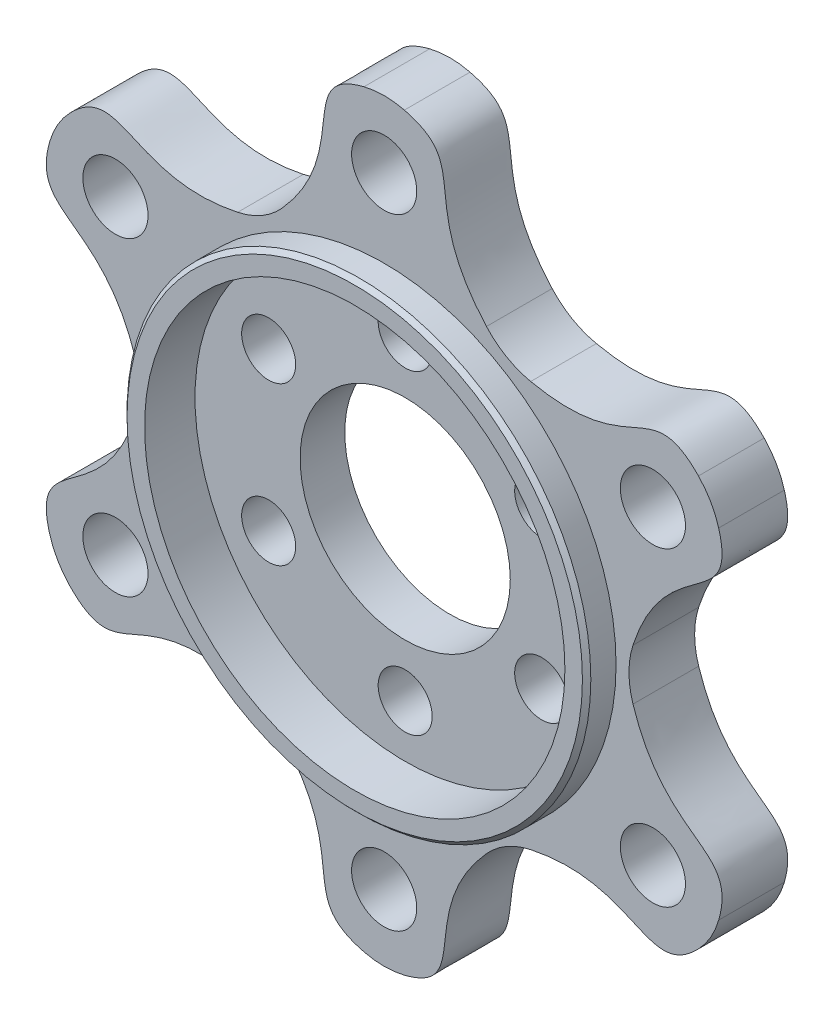
SolidWorks part; units mm, degrees
ref_plane "Front Plane" through (0, 0, 0) normal (0, 0, 1) x (1, 0, 0)
ref_plane "Top Plane" through (0, 0, 0) normal (0, 1, 0) x (1, 0, 0)
ref_plane "Right Plane" through (0, 0, 0) normal (1, 0, 0) x (0, 0, -1)
sketch "Sketch1" plane through (0, 0, 0) normal (0, 0, 1) x (1, 0, 0)
  line L0 (0, -55) -> (0, 55) construction
  line L1 (0, 0) -> (0, 45.72) construction
  circle A0 centre (0, 0) radius 12.7
  circle A1 centre (0, 0) radius 45.72
  circle A2 centre (0, 19.05) radius 3.2639
  circle A3 centre (16.4978, 9.525) radius 3.2639
  circle A4 centre (16.4978, -9.525) radius 3.2639
  circle A5 centre (0, -19.05) radius 3.2639
  circle A6 centre (-16.4978, -9.525) radius 3.2639
  circle A7 centre (-16.4978, 9.525) radius 3.2639
  circle A8 centre (0, 37.5) radius 3.937
  circle A10 centre (32.476, 18.75) radius 3.937
  circle A11 centre (32.476, -18.75) radius 3.937
  circle A12 centre (0, -37.5) radius 3.937
  circle A13 centre (-32.476, -18.75) radius 3.937
  circle A14 centre (-32.476, 18.75) radius 3.937
  point P21 (0, 0)
  point P36 (0, 0)
  dimension "D1" = 25.4
  dimension "D2" = 91.44
  dimension "D3" = 6.5278
  dimension "D6" = 7.874
  dimension "D4" = 19.05
  dimension "D8" = 37.5
  dimension "D5" = 6
  dimension "D7" = 6
extrude "Boss-Extrude3" add sketch "Sketch1" along normal blind 7.9375
sketch "Sketch2" plane through (0, 0, 7.9375) normal (0, 0, 1) x (1, 0, 0)
  line L0 (0, -55) -> (0, 55) construction
  line L1 (-32.476, 18.75) -> (0, 37.5) construction
  line L2 (-16.238, 28.125) -> (-6.35, 10.9985) construction
  line L3 (16.1981, 28.148) -> (6.3101, 11.0215) construction
  line L6 (32.476, -18.75) -> (32.476, 18.75) construction
  line L7 (32.476, 18.75) -> (0, 37.5) construction
  line L8 (55, 0) -> (-55, 0) construction
  circle A0 centre (0, 0) radius 27.94 construction
  circle A1 centre (0, 0) radius 45.72 construction
  circle A2 centre (0, 0) radius 12.7 construction
  circle A3 centre (0, 0) radius 45.72
  spline S0 degree 3 poles (-14.625, 25.3312) (-1.5745, 37.1177) (-13.1193, 43.9586) (0, 45.72) knots 0 0 0 0 1 1 1 1
  spline S1 degree 3 poles (14.625, 25.3312) (1.5745, 37.1177) (13.1193, 43.9586) (0, 45.72) knots 0 0 0 0 1 1 1 1
  spline S2 degree 3 poles (-29.25, 0) (-32.9321, 17.1953) (-44.6289, 10.6177) (-39.5947, 22.86) knots 0 0 0 0 1 1 1 1
  spline S3 degree 3 poles (-14.625, 25.3312) (-31.3576, 19.9224) (-31.5096, 33.3409) (-39.5947, 22.86) knots 0 0 0 0 1 1 1 1
  spline S4 degree 3 poles (-14.625, -25.3312) (-31.3576, -19.9224) (-31.5096, -33.3409) (-39.5947, -22.86) knots 0 0 0 0 1 1 1 1
  spline S5 degree 3 poles (-29.25, 0) (-32.9321, -17.1953) (-44.6289, -10.6177) (-39.5947, -22.86) knots 0 0 0 0 1 1 1 1
  spline S6 degree 3 poles (14.625, -25.3312) (31.3576, -19.9224) (31.5096, -33.3409) (39.5947, -22.86) knots 0 0 0 0 1 1 1 1
  spline S7 degree 3 poles (29.25, 0) (32.9321, -17.1953) (44.6289, -10.6177) (39.5947, -22.86) knots 0 0 0 0 1 1 1 1
  spline S8 degree 3 poles (14.625, -25.3312) (1.5745, -37.1177) (13.1193, -43.9586) (0, -45.72) knots 0 0 0 0 1 1 1 1
  spline S9 degree 3 poles (-14.625, -25.3312) (-1.5745, -37.1177) (-13.1193, -43.9586) (0, -45.72) knots 0 0 0 0 1 1 1 1
  spline S10 degree 3 poles (29.25, 0) (32.9321, 17.1953) (44.6289, 10.6177) (39.5947, 22.86) knots 0 0 0 0 1 1 1 1
  spline S11 degree 3 poles (14.625, 25.3312) (31.3576, 19.9224) (31.5096, 33.3409) (39.5947, 22.86) knots 0 0 0 0 1 1 1 1
  point P5 (-16.238, 28.125)
  point P6 (16.1981, 28.148)
  circle M8 centre (0, 0) radius 45.72
  dimension "D1" = 55.88
  dimension "D2" = 18.796
  dimension "D3" = 29.25
extrude "Cut-Extrude1" cut sketch "Sketch2" against normal blind 22.86 contours S1 S11 M8 | S5 S2 A3 | S10 S7 A3 | S6 S8 A3 | S9 S4 M8 | S3 S0 M8 region at (38.672, 0, 7.9375) region at (19.336, 33.4909, 7.9375) region at (19.336, -33.4909, 7.9375) region at (-19.336, 33.4909, 7.9375) region at (-19.336, -33.4909, 7.9375) region at (-38.672, 0, 7.9375)
sketch "Sketch4" plane through (0, 0, 7.9375) normal (0, 0, 1) x (1, 0, 0)
  circle A0 centre (0, 0) radius 12.7 construction
  circle A1 centre (0, 0) radius 12.7 construction
  circle A2 centre (0, 0) radius 28.025
  circle A3 centre (0, 0) radius 25.4
  dimension "D1" = 56.05
  dimension "D2" = 50.8
extrude "Boss-Extrude4" add sketch "Sketch4" along normal blind 3.556 contours A2 | A3
ref_plane "Plane1" through (0, 0, 0) normal (1, 0, 0) x (0, 0, -1)
ref_plane "Plane2" through (0, 0, 0) normal (-0.5, -0.866, 0) x (-0.866, 0.5, 0)
ref_plane "Plane3" through (0, 0, 0) normal (-0.5, 0.866, 0) x (0.866, 0.5, 0)
ref_axis "Axis1" through (0, 0, 7.9375) along (0, 0, -1)
fillet "Fillet1" radius 10 12 edges at (29.25, 0, 3.9688) (39.5947, -22.86, 3.9688) (0, -45.72, 3.9688) (14.625, -25.3312, 3.9688) (-14.625, -25.3312, 3.9688) (-39.5947, -22.86, 3.9688) (-29.25, 0, 3.9688) (-39.5947, 22.86, 3.9688) (-14.625, 25.3312, 3.9688) (14.625, 25.3312, 3.9688) (39.5947, 22.86, 3.9688) (0, 45.72, 3.9688)
chamfer "Chamfer1" distance 0.508 angle 45 1 edges at (28.025, 0, 11.4935)
sketch "Sketch7" plane through (0, 0, 7.9375) normal (0, 0, 1) x (1, 0, 0)
  circle A0 centre (0, 0) radius 25.4
extrude "Cut-Extrude2" cut sketch "Sketch7" against normal blind 2.54
